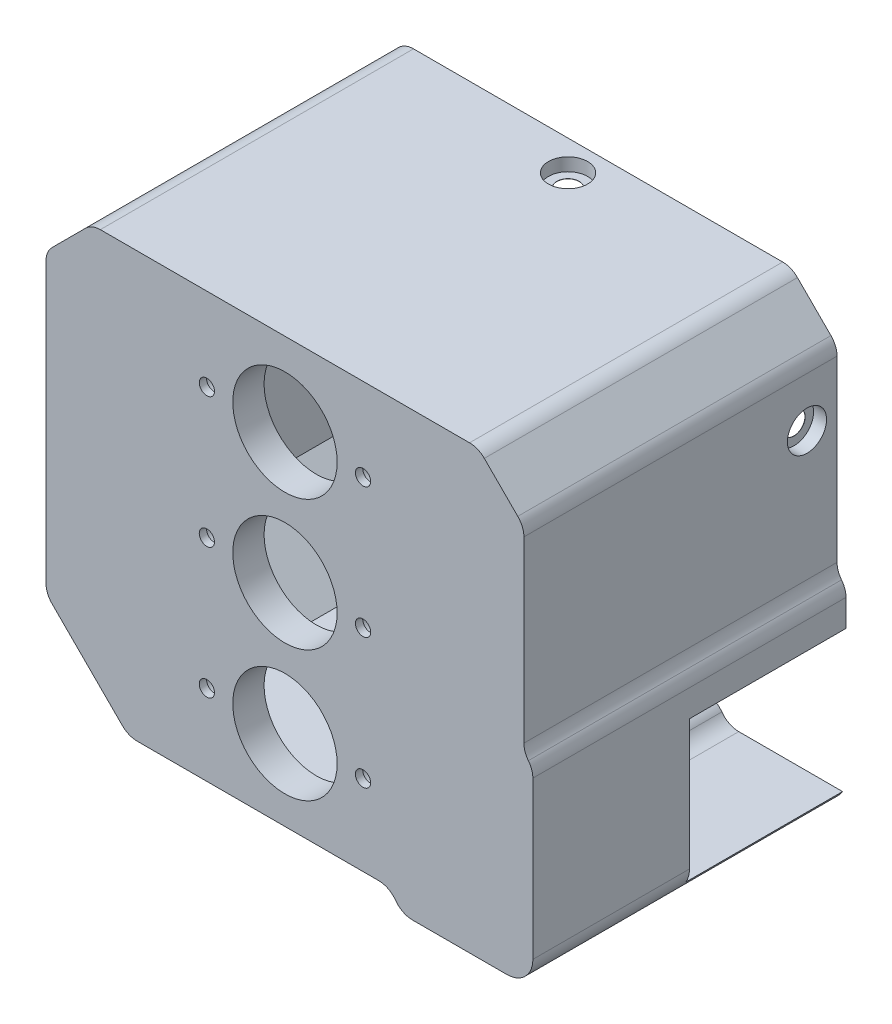
SolidWorks part; units mm, degrees
ref_plane "Front Plane" through (0, 0, 0) normal (0, 0, 1) x (1, 0, 0)
ref_plane "Top Plane" through (0, 0, 0) normal (0, 1, 0) x (1, 0, 0)
ref_plane "Right Plane" through (0, 0, 0) normal (1, 0, 0) x (0, 0, -1)
sketch "Sketch1" plane through (0, 0, 0) normal (0, 0, 1) x (1, 0, 0)
  line L0 (-19.0397, -28.067) -> (-29.0727, -18.034)
  line L1 (13.9018, -28.067) -> (-19.0397, -28.067)
  line L2 (29.0727, -6.8325) -> (29.0727, 18.034)
  line L4 (-29.0727, -18.034) -> (-29.0727, 18.034)
  line L5 (0, 28.067) -> (0, -28.067) construction
  line L6 (29.0727, 0) -> (-29.0727, 0) construction
  line L9 (29.0727, -6.8325) -> (30.1625, -6.8325)
  line L10 (30.1625, 26.9875) -> (30.1625, -26.9875) construction
  line L11 (30.1625, -6.8325) -> (30.1625, -26.9875)
  line L12 (26.9875, -30.1625) -> (13.9018, -30.1625)
  line L13 (26.9875, -30.1625) -> (-26.9875, -30.1625) construction
  line L14 (13.9018, -30.1625) -> (13.9018, -28.067)
  line L19 (-28.5296, 18.5771) -> (-23.5131, 23.5936)
  line L20 (-23.5131, 23.5936) -> (23.5131, 23.5936)
  line L21 (23.5131, 23.5936) -> (28.5296, 18.5771)
  line L22 (-29.0727, 18.034) -> (-23.5131, 23.5936)
  line L23 (-23.5131, 23.5936) -> (23.5131, 23.5936)
  line L24 (23.5131, 23.5936) -> (29.0727, 18.034)
  arc A0 (30.1625, -26.9875) -> (26.9875, -30.1625) centre (26.9875, -26.9875) cw
  point P0 (0, 0)
  point P1 (-29.0727, 28.067)
  point P3 (29.0727, 28.067)
  point P8 (-29.0727, -28.067)
  dimension "D3" = 1.8542
  dimension "D1" = 28.067
  dimension "D2" = 1.8542
  dimension "D6" = 10.033
  dimension "D7" = 10.033
extrude "Boss-Extrude1" add sketch "Sketch1" along normal blind 38.1
shell "Shell1" thickness 1.6002 removed face at (8.0612, -7.7123, 0)
sketch "Sketch14" plane through (0, 0, 36.4998) normal (0, 0, -1) x (-1, 0, 0)
  line L11 (-15.502, -26.4668) -> (18.3768, -26.4668)
  line L12 (18.3768, -26.4668) -> (27.4725, -17.3712)
  line L13 (27.4725, -17.3712) -> (27.4725, 17.3712)
  line L14 (27.4725, 17.3712) -> (22.8503, 21.9934)
  line L15 (27.4725, 17.3712) -> (22.8503, 21.9934)
  line L16 (22.8503, 21.9934) -> (-22.8503, 21.9934)
  line L17 (-27.4725, 17.3712) -> (-27.4725, -8.4327)
  line L18 (-27.4725, -8.4327) -> (-28.5623, -8.4327)
  line L19 (-28.5623, -8.4327) -> (-28.5623, -26.9875)
  line L20 (-26.9875, -28.5623) -> (-15.502, -28.5623)
  line L21 (-15.502, -28.5623) -> (-15.502, -26.4668)
  line L22 (-15.502, -26.4668) -> (18.3768, -26.4668)
  line L23 (18.3768, -26.4668) -> (27.4725, -17.3712)
  line L24 (27.4725, -17.3712) -> (27.4725, 17.3712)
  line L25 (22.8503, 21.9934) -> (-22.8503, 21.9934)
  line L26 (-22.8503, 21.9934) -> (-27.4725, 17.3712)
  line L27 (-22.8503, 21.9934) -> (-27.4725, 17.3712)
  line L28 (-27.4725, 17.3712) -> (-27.4725, -8.4327)
  line L29 (-27.4725, -8.4327) -> (-28.5623, -8.4327)
  line L30 (-28.5623, -8.4327) -> (-28.5623, -26.9875)
  line L31 (-26.9875, -28.5623) -> (-15.502, -28.5623)
  line L32 (-15.502, -28.5623) -> (-15.502, -26.4668)
  arc A1 (-28.5623, -26.9875) -> (-26.9875, -28.5623) centre (-26.9875, -26.9875) ccw
  arc A2 (-28.5623, -26.9875) -> (-26.9875, -28.5623) centre (-26.9875, -26.9875) ccw
  dimension "D1" = 0
extrude "Boss-Extrude2" add sketch "Sketch14" along normal blind 3.81 from surface starting at face at (8.0612, -7.7123, 38.1)
fillet "Fillet1" radius 2.54 10 edges at (13.9018, -28.067, 19.05) (15.502, -26.4668, 17.145) (28.5623, -8.4327, 17.145) (29.0727, -6.8325, 19.05) (-29.0727, -18.034, 19.05) (-19.0397, -28.067, 19.05) (29.0727, 18.034, 19.05) (23.5131, 23.5936, 19.05) (-23.5131, 23.5936, 19.05) (-29.0727, 18.034, 19.05)
fillet "Fillet2" radius 2.54 4 edges at (13.9018, -30.1625, 19.05) (15.502, -28.5623, 17.145) (30.1625, -6.8325, 19.05) (27.4725, -8.4327, 17.145)
sketch "Sketch4" plane through (30.1625, 0, 0) normal (1, 0, 0) x (0, 0, -1)
  line L0 (0, -26.9875) -> (0, -7.8912) construction
  line L1 (0, -11.1633) -> (-19.05, -11.1633)
  line L2 (0, -11.1633) -> (0, -28.5623)
  line L3 (0, -28.5623) -> (-19.05, -28.5623)
  line L4 (-19.05, -11.1633) -> (-19.05, -28.5623)
  line L5 (-34.29, -28.5623) -> (0, -28.5623) construction
  dimension "D1" = 17.399
  dimension "D2" = 19.05
extrude "Cut-Extrude1" cut sketch "Sketch4" against normal up to next
hole_wizard "CBORE for #2 Pan Head Machine Screw1" positions "Sketch15" profile "Sketch16" counterbore size "#2" standard "ANSI Inch" end condition up to next
sketch "Sketch15" plane through (-29.0727, 0, 0) normal (-1, 0, 0) x (0, 0, 1)
  point P0 (3.6565, 0)
sketch "Sketch16" plane through (-29.0727, 0, 3.6565) normal (0, 1, 0) x (0, 0, 1)
  line L0 (0, 0) -> (0, 1.6002)
  line L1 (0, 1.6002) -> (1.3525, 1.6002)
  line L3 (1.3525, 1.6002) -> (1.3525, 1.5748)
  line L4 (1.3525, 1.5748) -> (2.3812, 1.5748)
  line L5 (2.3812, 1.5748) -> (2.3812, 0)
  line L7 (2.3812, 0) -> (0, 0)
  line L11 (0, -6.35) -> (0, 107.95) construction
  dimension "Thru Hole Dia." = 2.7051
  dimension "Thru Hole Depth" = 1.6002
  dimension "C'Bore Dia." = 4.7625
  dimension "C'Bore Depth" = 1.5748
hole_wizard "CBORE for #2 Pan Head Machine Screw2" positions "Sketch17" profile "Sketch18" counterbore size "#2" standard "ANSI Inch" end condition up to next
sketch "Sketch17" plane through (0, 23.5936, 0) normal (0, 1, 0) x (1, 0, 0)
  point P0 (0, -3.6565)
sketch "Sketch18" plane through (0, 23.5936, 3.6565) normal (1, 0, 0) x (0, 0, 1)
  line L0 (0, 0) -> (0, 1.6002)
  line L1 (0, 1.6002) -> (1.3525, 1.6002)
  line L3 (1.3525, 1.6002) -> (1.3526, 1.5748)
  line L4 (1.3526, 1.5748) -> (2.3812, 1.5748)
  line L5 (2.3812, 1.5748) -> (2.3812, 0)
  line L7 (2.3812, 0) -> (0, 0)
  line L11 (0, -6.35) -> (0, 107.95) construction
  dimension "Thru Hole Dia." = 2.7051
  dimension "Thru Hole Depth" = 1.6002
  dimension "C'Bore Dia." = 4.7625
  dimension "C'Bore Depth" = 1.5748
hole_wizard "CBORE for #2 Pan Head Machine Screw3" positions "Sketch19" profile "Sketch20" counterbore size "#2" standard "ANSI Inch" end condition up to next
sketch "Sketch19" plane through (29.0727, 0, 0) normal (1, 0, 0) x (0, 0, -1)
  point P0 (-3.6565, 10.9575)
sketch "Sketch20" plane through (29.0727, 10.9575, 3.6565) normal (0, 1, 0) x (0, 0, -1)
  line L0 (0, 0) -> (0, 1.6002)
  line L1 (0, 1.6002) -> (1.3525, 1.6002)
  line L3 (1.3525, 1.6002) -> (1.3526, 1.5748)
  line L4 (1.3526, 1.5748) -> (2.3812, 1.5748)
  line L5 (2.3812, 1.5748) -> (2.3812, 0)
  line L7 (2.3812, 0) -> (0, 0)
  line L11 (0, -6.35) -> (0, 107.95) construction
  dimension "Thru Hole Dia." = 2.7051
  dimension "Thru Hole Depth" = 1.6002
  dimension "C'Bore Dia." = 4.7625
  dimension "C'Bore Depth" = 1.5748
hole_wizard "CBORE for #2 Pan Head Machine Screw4" positions "Sketch21" profile "Sketch22" counterbore size "#2" standard "ANSI Inch" end condition up to next
sketch "Sketch21" plane through (0, -28.067, 0) normal (0, -1, 0) x (-1, 0, 0)
  point P0 (0, -3.6565)
sketch "Sketch22" plane through (0, -28.067, 3.6565) normal (1, 0, 0) x (0, 0, -1)
  line L0 (0, 0) -> (0, 1.6002)
  line L1 (0, 1.6002) -> (1.3525, 1.6002)
  line L3 (1.3525, 1.6002) -> (1.3526, 1.5748)
  line L4 (1.3526, 1.5748) -> (2.3812, 1.5748)
  line L5 (2.3812, 1.5748) -> (2.3812, 0)
  line L7 (2.3812, 0) -> (0, 0)
  line L11 (0, -6.35) -> (0, 107.95) construction
  dimension "Thru Hole Dia." = 2.7051
  dimension "Thru Hole Depth" = 1.6002
  dimension "C'Bore Dia." = 4.7625
  dimension "C'Bore Depth" = 1.5748
hole_wizard "Hole1" positions "Sketch23" profile "Sketch24" legacy
sketch "Sketch23" plane through (0, 0, 34.29) normal (0, 0, -1) x (-1, 0, 0)
  point P0 (-9.5, 13.4938)
  point P3 (9.5, 13.4937)
  point P6 (9.5, -2.3813)
  point P9 (-9.5, -2.3813)
  point P12 (-9.5, -18.2562)
  point P15 (9.5, -18.2563)
sketch "Sketch24" plane through (9.5, 13.4938, 34.29) normal (1, 0, 0) x (0, 1, 0)
  line L0 (0, 0) -> (0, 2.921)
  line L1 (0, 2.921) -> (1.4986, 2.921)
  line L2 (1.4986, 2.921) -> (1.6383, 0)
  line L3 (1.6383, 0) -> (0, 0)
  line L4 (0, 110) -> (0, -10) construction
  dimension "Minor Diameter" = 2.9972
  dimension "Depth" = 2.921
  dimension "Major Diameter" = 3.2766
hole_wizard "#0 Clearance Hole1" positions "Sketch25" profile "Sketch26" hole size "#0" standard "ANSI Inch" end condition up to next
sketch "Sketch25" plane through (0, 0, 34.29) normal (0, 0, -1) x (-1, 0, 0)
  point P0 (-9.5, 13.4938)
  point P3 (9.5, 13.4937)
  point P6 (-9.5, -2.3812)
  point P9 (9.5, -2.3813)
  point P12 (-9.5, -18.2562)
  point P15 (9.5, -18.2563)
sketch "Sketch26" plane through (9.5, 13.4938, 34.29) normal (1, 0, 0) x (0, 1, 0)
  line L0 (0, 0) -> (0, 3.81)
  line L1 (0, 3.81) -> (0.9271, 3.81)
  line L2 (0.9271, 3.81) -> (0.9271, 0)
  line L5 (0.9271, 0) -> (0, 0)
  line L11 (0, -6.35) -> (0, 107.95) construction
  dimension "Thru Hole Dia." = 1.8542
  dimension "Thru Hole Depth" = 3.81
sketch "Sketch27" plane through (0, 0, 38.1) normal (0, 0, 1) x (1, 0, 0)
  circle A0 centre (0, 13.4937) radius 6.35
  circle A2 centre (0, -2.3813) radius 6.35
  circle A3 centre (0, -18.2813) radius 6.35
  dimension "D1" = 12.7
extrude "Cut-Extrude2" cut sketch "Sketch27" against normal up to next
